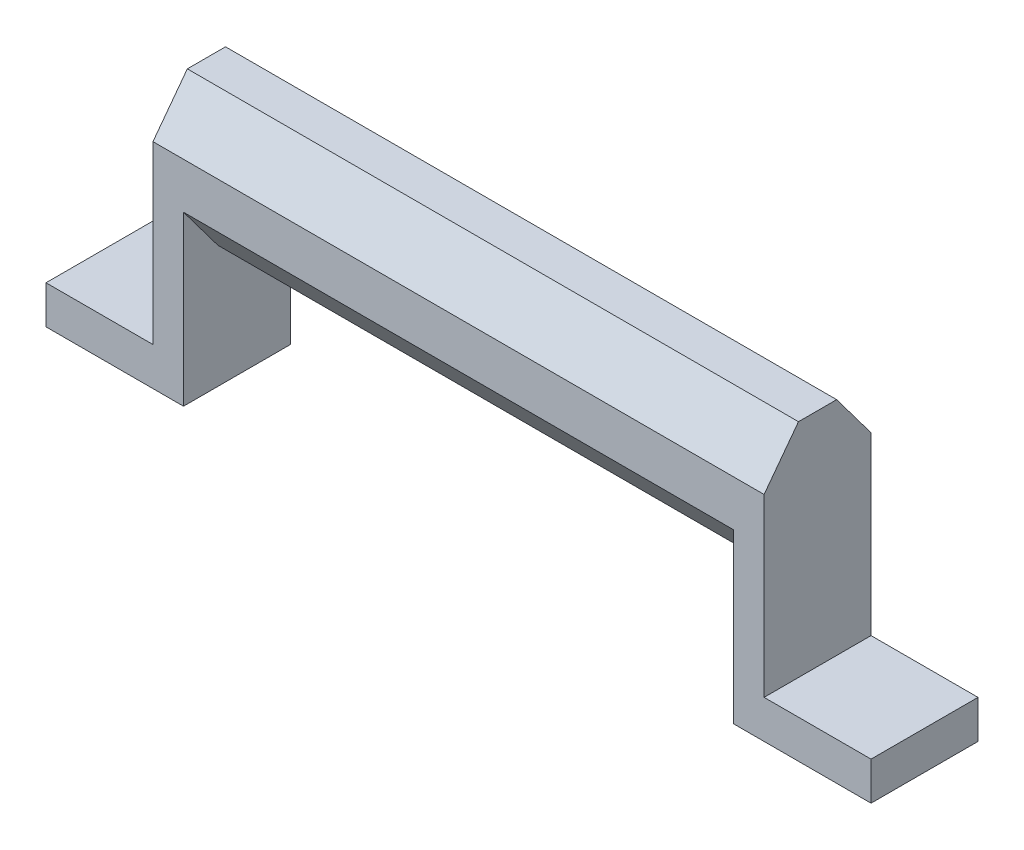
SolidWorks part; units mm, degrees
ref_plane "Front Plane" through (0, 0, 0) normal (0, 0, 1) x (1, 0, 0)
ref_plane "Top Plane" through (0, 0, 0) normal (0, 1, 0) x (1, 0, 0)
ref_plane "Right Plane" through (0, 0, 0) normal (1, 0, 0) x (0, 0, -1)
sketch "Sketch1" plane through (0, 0, 0) normal (1, 0, 0) x (0, 0, -1)
  line L0 (0, -248.6209) -> (0, 12182.4256) construction
  line L1 (-8.89, -3.81) -> (-3.175, -11.43)
  line L2 (3.175, -11.43) -> (-3.175, -11.43)
  line L4 (3.175, 11.43) -> (-3.175, 11.43)
  line L6 (-8.89, 3.81) -> (8.89, 3.81) construction
  line L7 (-8.89, -3.81) -> (8.89, -3.81) construction
  line L9 (8.89, -3.81) -> (8.89, 3.81)
  line L11 (-8.89, -3.81) -> (-8.89, 3.81)
  line L12 (-3.175, -11.43) -> (-3.175, 11.43) construction
  line L13 (3.175, 11.43) -> (3.175, -11.43) construction
  line L15 (-8.89, -3.81) -> (8.89, -3.81)
  line L16 (3.175, -11.43) -> (8.89, -3.81)
  line L17 (8.89, 3.81) -> (3.175, 11.43)
  line L18 (-3.175, 11.43) -> (-8.89, 3.81)
  line L19 (-8.89, -3.81) -> (-8.89, -31.75)
  line L20 (-8.89, -31.75) -> (8.89, -31.75)
  line L21 (8.89, -3.81) -> (8.89, -31.75)
  line L22 (-8.89, -31.75) -> (8.89, -31.75)
  line L23 (-8.89, -31.75) -> (-8.89, -25.4)
  line L24 (-8.89, -25.4) -> (8.89, -25.4)
  line L25 (8.89, -31.75) -> (8.89, -25.4)
  point P1 (0, 0)
  point P8 (0, 0)
  dimension "D1" = 7.62
  dimension "D2" = 22.86
  dimension "D3" = 17.78
  dimension "D4" = 6.35
  dimension "D5" = 9.525
  dimension "D6" = 8.89
  dimension "D7" = 11.43
  dimension "D8" = 20.32
  dimension "D9" = 6.35
extrude "Boss-Extrude1" add sketch "Sketch1" along normal blind 5.08 contours L24 L19 L20 L21 | L19 L24 L21 L16 L2 L1 | L2 L16 L15 L1 | L4 L18 L11 L15 L9 L17 region at (0, -7.0184, 0) region at (0, 2.8372, 0) region at (0, -16.9941, 0) region at (0, -28.575, 0)
extrude "Boss-Extrude2" add sketch "Sketch1<3>" along normal blind 50.8 contours L2 L16 L15 L1 | L4 L18 L11 L15 L9 L17 region at (0, -7.0184, 0) region at (0, 2.8372, 0)
sketch "Sketch1<3>" plane through (0, 0, 0) normal (1, 0, 0) x (0, 0, -1) same geometry as "Sketch1"
extrude "Boss-Extrude3" add sketch "Sketch1<4>" against normal blind 17.78 contours L24 L19 L20 L21 region at (0, -28.575, 0)
sketch "Sketch1<4>" plane through (0, 0, 0) normal (1, 0, 0) x (0, 0, -1) same geometry as "Sketch1"
ref_plane "Plane1" through (50.8, 0, 0) normal (1, 0, 0) x (0, 0, -1)
mirror "Mirror1" about plane through (50.8, 0, 0) normal (1, 0, 0) of bodies 103
